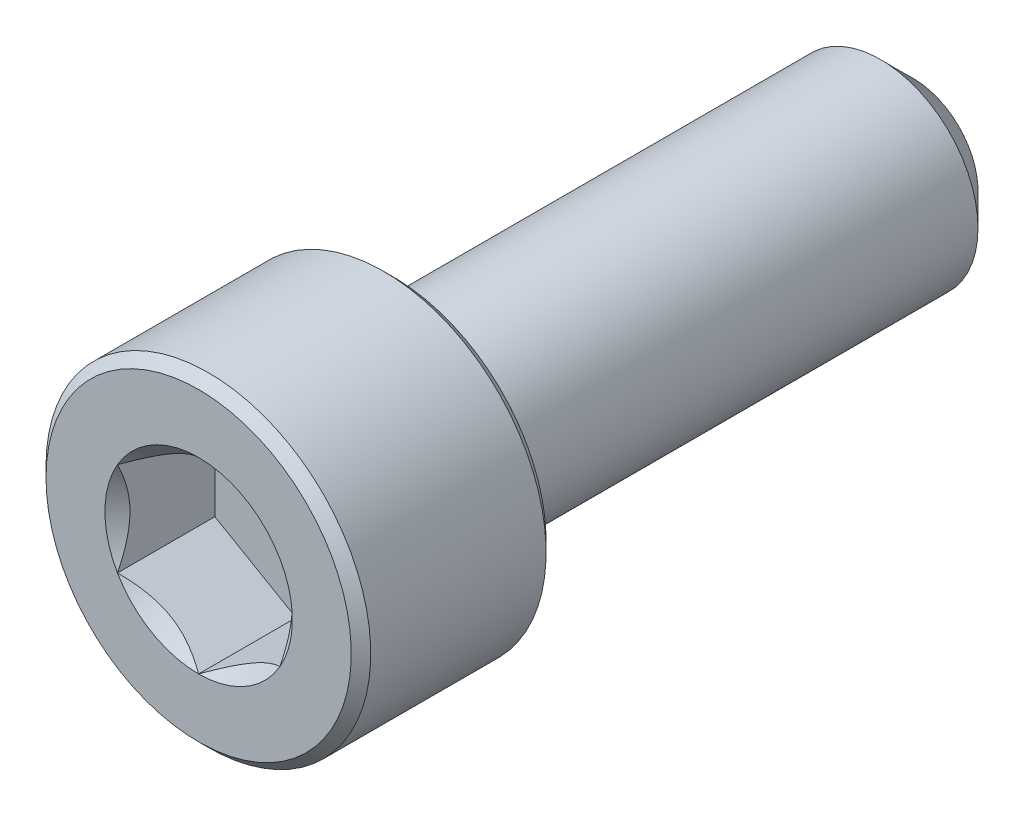
SolidWorks part; units mm, degrees
ref_plane "Front Plane" through (0, 0, 0) normal (0, 0, 1) x (1, 0, 0)
ref_plane "Top Plane" through (0, 0, 0) normal (0, 1, 0) x (1, 0, 0)
ref_plane "Right Plane" through (0, 0, 0) normal (1, 0, 0) x (0, 0, -1)
sketch "Sketch1" plane through (0, 0, 0) normal (1, 0, 0) x (0, 0, -1)
  line L0 (-11, 0) -> (11, 0) construction
  line L1 (11, 0) -> (11, 2) construction
  line L2 (11, 2) -> (10, 3) construction
  line L3 (10, 3) -> (-5, 3) construction
  line L5 (-5, 3) -> (-5, 5) construction
  line L6 (-5, 5) -> (-11, 5) construction
  line L7 (-11, 5) -> (-11, 0) construction
  line L8 (11, 2) -> (11, 3) construction
  line L9 (10.9375, 3.1083) -> (11.4375, 2.2422) construction
  line L10 (11.4375, 2.2422) -> (11.9375, 3.1083) construction
  line L11 (11.9375, 3.1083) -> (10.9375, 3.1083) construction
  line L12 (11.4375, 3.1083) -> (11.4375, 3) construction
  line L13 (11.4375, 2.2422) -> (11.4375, 2.3505) construction
  line L14 (11.375, 2.3505) -> (11.5, 2.3505) construction
  line L15 (11, 3) -> (11.875, 3) construction
  line L16 (10.9687, 3.0541) -> (11.9062, 3.0541) construction
  line L17 (11, 0) -> (11, -3) construction
  line L18 (-5.3, 5) -> (-5, 4.7) construction
  line L19 (-10.7, 5) -> (-11, 4.7) construction
  point P0 (-11, 2.5)
  point P3 (7.5, 3)
  point P4 (0, 0)
  point P22 (11.4375, 2.3505)
  point P24 (-5, 3)
  point P25 (11.4375, 3)
  point P28 (11.4375, 3.0541)
  point P29 (7.5, -3)
  point P31 (-8, 5)
  point P37 (-6.05, 5)
  point P38 (-10.55, 5)
  point P41 (-8, 0)
  dimension "head height" = 6
  dimension "D1" = 45
  dimension "Head Diameter" = 10
  dimension "Thread Size" = 6
  dimension "drive size" = 5
  dimension "Thread Pitch" = 1
  dimension "D2" = 0.125
  dimension "D3" = 1
  dimension "D4" = 3.5
  dimension "D7" = 0.3
  dimension "D8" = 0.3
  dimension "D9" = 0.3
  dimension "D10" = 0.15
  dimension "D11" = 0.75
  dimension "length" = 16
  dimension "Drive Depth" = 3
sketch "Sketch2" plane through (0, 0, 0) normal (1, 0, 0) x (0, 0, -1)
  line L1 (-10.7, 5) -> (-5.3, 5)
  line L4 (10, 3) -> (11, 2)
  line L5 (11, 2) -> (11, 0)
  line L6 (-5.3, 5) -> (-5, 4.7) construction
  line L7 (11, 0) -> (-11, 0)
  line L8 (-10.7, 5) -> (-11, 4.7) construction
  line L9 (-5.3, 5) -> (-5, 4.7)
  line L10 (-10.7, 5) -> (-11, 4.7)
  line L11 (-11, 4.7) -> (-11, 0)
  line L12 (-5, 4.7) -> (-5, 3)
  line L13 (-5, 3) -> (10, 3)
revolve "Revolve1" add sketch "Sketch2" angle 360 about L7
sketch "Sketch3" plane through (0, 0, 11) normal (0, 0, 1) x (1, 0, 0)
  line L1 (0, 2.8868) -> (-2.5, 1.4434)
  line L2 (-2.5, 1.4434) -> (-2.5, -1.4434)
  line L3 (-2.5, -1.4434) -> (0, -2.8868)
  line L4 (0, -2.8868) -> (2.5, -1.4434)
  line L5 (2.5, -1.4434) -> (2.5, 1.4434)
  line L6 (2.5, 1.4434) -> (0, 2.8868)
  circle A0 centre (0, 0) radius 2.5 construction
  dimension "D1" = 5
extrude "Cut-Extrude1" cut sketch "Sketch3" against normal up to vertex (3 mm away) up to point (0, 0, 8)
sketch "Sketch4" plane through (0, 0, 11) normal (0, 0, 1) x (1, 0, 0)
  circle A0 centre (0, 0) radius 2.8868
extrude "Cut-Extrude2" cut sketch "Sketch4" against normal blind 0.5 draft 45
ref_plane "Plane1" [suppressed] through (0, 0, 5) normal (0, 0, 1) x (1, 0, 0)
split "Split1" [suppressed] bodies to split 106
sketch "Sketch6" [suppressed] plane through (0, 0, -11) normal (0, 0, -1) x (-1, 0, 0)
  circle A0 centre (0, 0) radius 3
curve "Helix/Spiral1" [suppressed] pitch 1 height 17 turns 17
sketch "Sketch7" [suppressed] plane through (0, 0, 0) normal (1, 0, 0) x (0, 0, -1)
  line L0 (10.9687, 3.0541) -> (11.9062, 3.0541)
  line L1 (11.9062, 3.0541) -> (11.5, 2.3505)
  line L2 (11.5, 2.3505) -> (11.375, 2.3505)
  line L3 (11.375, 2.3505) -> (10.9687, 3.0541)
sweep "Cut-Sweep1" [suppressed] cut profiles "Sketch7" path "Helix/Spiral1"
sketch "Sketch8" [suppressed] plane through (0, 0, 5) normal (0, 0, -1) x (-1, 0, 0)
  circle A0 centre (0, 0) radius 3
extrude "Boss-Extrude1" [suppressed] add sketch "Sketch8" along normal through all draft 45
ref_plane "Plane2" [suppressed] through (0, 0, 8) normal (0, 0, 1) x (1, 0, 0)
sketch "Sketch9" [suppressed] plane through (0, 0, 8) normal (0, 0, 1) x (1, 0, 0)
  line L0 (0, 4.8625) -> (0.1309, 4.9983)
  line L1 (0, 4.8625) -> (-0.1309, 4.9983)
  line L2 (0, 5) -> (0, 0) construction
  line L3 (-0.1309, 4.9983) -> (0, 0) construction
  line L4 (0, 0) -> (0.1309, 4.9983) construction
  arc A0 (0.1309, 4.9983) -> (-0.1309, 4.9983) centre (0, 0) ccw
  circle A1 centre (0, 0) radius 4.8625 construction
  dimension "D2" = 9.725
  dimension "D3" = 3
extrude "Cut-Extrude4" [suppressed] cut sketch "Sketch9" against normal up to vertex and the other way up to vertex up to point (0, 5, 6.05) other way up to point (0, 5, 10.55)
pattern_circular "CirPattern2" [suppressed] count 96 over 360 about axis through (0, 0, 11) along (0, 0, -1) of bodies 113
equation "\"D2@Sketch1\" = \"Thread Pitch@Sketch1\" / 8"
equation "\"D3@Sketch1\" = \"Thread Pitch@Sketch1\""
equation "\"D3@Helix/Spiral1\" = \"length@Sketch1\" + \"Thread Pitch@Sketch1\""
equation "\"D4@Helix/Spiral1\" = \"Thread Pitch@Sketch1\""
equation "\"D4@Sketch1\" = \"Thread Pitch@Sketch1\" * 3.5"
equation "\"D7@Sketch1\"=\"head height@Sketch1\"*.05"
equation "\"D8@Sketch1\"=\"D7@Sketch1\""
equation "\"D9@Sketch1\"=\"D7@Sketch1\""
equation "\"D10@Sketch1\"=\"D7@Sketch1\"/2"
equation "\"D11@Sketch1\"=\"D10@Sketch1\"*5"
equation "\"D1@CirPattern2\"=( 360 / \"D3@Sketch9\" )*0.8"
equation "\"D1@Sketch3\" = \"drive size@Sketch1\""
equation "\"D2@Sketch9\"=\"Head Diameter@Sketch1\" * 0.9725"
